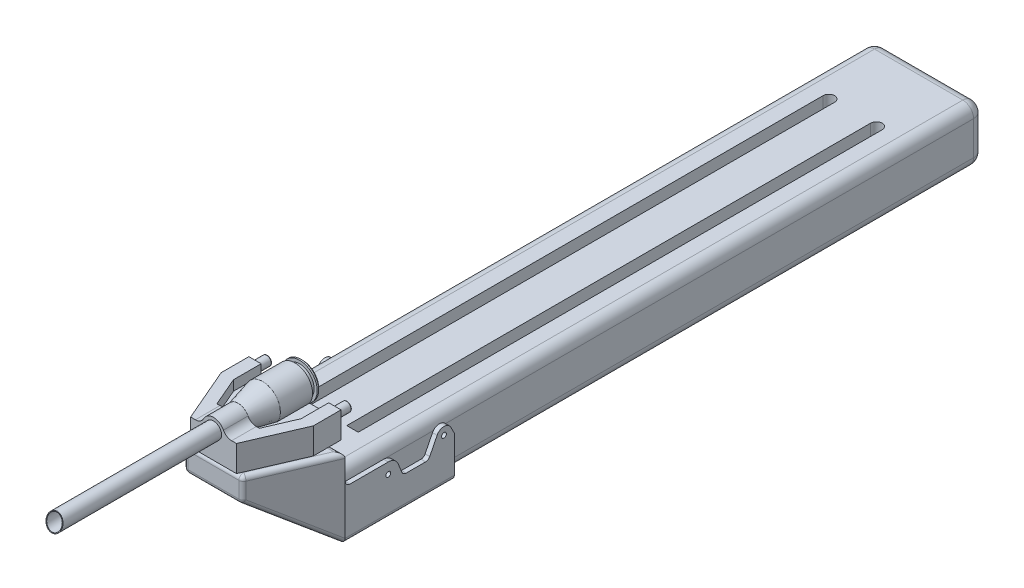
SolidWorks part; units mm, degrees
material "6061-T6 (SS)"
ref_plane "Front Plane" through (0, 0, 0) normal (0, 0, 1) x (1, 0, 0)
ref_plane "Top Plane" through (0, 0, 0) normal (0, 1, 0) x (1, 0, 0)
ref_plane "Right Plane" through (0, 0, 0) normal (1, 0, 0) x (0, 0, -1)
sketch "Sketch1" plane through (0, 0, 0) normal (0, 0, 1) x (1, 0, 0)
  line L1 (0, 0) -> (71.5, 0)
  line L2 (0, 0) -> (0, 36)
  line L3 (0, 36) -> (71.5, 36)
  line L4 (71.5, 0) -> (71.5, 36)
  dimension "D1" = 71.5
  dimension "D2" = 36
extrude "Boss-Extrude1" add sketch "Sketch1" along normal blind 419.1
sketch "Sketch2" plane through (0, 36, 0) normal (0, 1, 0) x (1, 0, 0)
  line L0 (71.5, -348.1) -> (74.5, -348.1)
  line L1 (74.5, -348.1) -> (74.5, -419.1)
  line L2 (74.5, -419.1) -> (54.25, -466.1)
  line L3 (54.25, -466.1) -> (17.25, -466.1)
  line L4 (71.5, 0) -> (0, 0)
  line L5 (0, 0) -> (0, -419.1)
  line L6 (0, -419.1) -> (71.5, -419.1)
  line L7 (71.5, -419.1) -> (71.5, 0)
  line L8 (71.5, 0) -> (0, 0)
  line L9 (0, 0) -> (0, -419.1)
  line L10 (0, -419.1) -> (71.5, -419.1)
  line L11 (71.5, -419.1) -> (71.5, 0)
  line L12 (17.25, -466.1) -> (-3, -419.1)
  line L13 (-3, -419.1) -> (-3, -348.1)
  line L14 (-3, -348.1) -> (0, -348.1)
  point P12 (35.75, -466.1)
  point P15 (35.75, -419.1)
  line M10 (0, -419.1) -> (71.5, -419.1)
  line M11 (71.5, -419.1) -> (71.5, 0)
  dimension "D2" = 47
  dimension "D3" = 3
  dimension "D4" = 3
  dimension "D5" = 37
  dimension "D6" = 71
  dimension "D1" = 0
extrude "Boss-Extrude2" add sketch "Sketch2" against normal blind 39 contours L14 L13 L12 L3 L2 L1 L0 L9 M11 M10 region at (35.75, 36, 432.1438)
sketch "Sketch3" plane through (0, -3, 0) normal (0, -1, 0) x (1, 0, 0)
  line L0 (71.5, 348.1) -> (0, 348.1)
  line L6 (0, 0) -> (71.5, 0)
  line L7 (71.5, 0) -> (71.5, 348.1)
  line L8 (71.5, 348.1) -> (71.5, 419.1)
  line L9 (71.5, 419.1) -> (0, 419.1)
  line L10 (0, 419.1) -> (0, 348.1)
  line L11 (0, 348.1) -> (0, 0)
  line L12 (0, 0) -> (71.5, 0)
  line L13 (71.5, 0) -> (71.5, 348.1)
  line L14 (71.5, 348.1) -> (71.5, 419.1)
  line L15 (71.5, 419.1) -> (0, 419.1)
  line L16 (0, 419.1) -> (0, 348.1)
  line L17 (0, 348.1) -> (0, 0)
  line M8 (0, 348.1) -> (0, 419.1)
  line M9 (0, 419.1) -> (71.5, 419.1)
  line M10 (71.5, 419.1) -> (71.5, 348.1)
  dimension "D1" = 0
extrude "Boss-Extrude3" add sketch "Sketch3" against normal up to surface (3 mm away) contours L0 M10 M9 M8 region at (35.75, -3, 383.6) up to face at (35.75, 0, 255.7333)
sketch "Sketch4" plane through (0, 36, 0) normal (0, 1, 0) x (1, 0, 0)
  line L0 (-3, -419.1) -> (74.5, -419.1)
  line L10 (0, 0) -> (0, -348.1)
  line L11 (0, -348.1) -> (-3, -348.1)
  line L12 (-3, -348.1) -> (-3, -419.1)
  line L13 (-3, -419.1) -> (17.25, -466.1)
  line L14 (17.25, -466.1) -> (54.25, -466.1)
  line L15 (54.25, -466.1) -> (74.5, -419.1)
  line L16 (74.5, -419.1) -> (74.5, -348.1)
  line L17 (74.5, -348.1) -> (71.5, -348.1)
  line L18 (71.5, -348.1) -> (71.5, 0)
  line L19 (71.5, 0) -> (0, 0)
  line L20 (0, 0) -> (0, -348.1)
  line L21 (0, -348.1) -> (-3, -348.1)
  line L22 (-3, -348.1) -> (-3, -419.1)
  line L23 (-3, -419.1) -> (17.25, -466.1)
  line L24 (17.25, -466.1) -> (54.25, -466.1)
  line L25 (54.25, -466.1) -> (74.5, -419.1)
  line L26 (74.5, -419.1) -> (74.5, -348.1)
  line L27 (74.5, -348.1) -> (71.5, -348.1)
  line L28 (71.5, -348.1) -> (71.5, 0)
  line L29 (71.5, 0) -> (0, 0)
  line M14 (-3, -419.1) -> (17.25, -466.1)
  line M15 (17.25, -466.1) -> (54.25, -466.1)
  line M16 (54.25, -466.1) -> (74.5, -419.1)
  dimension "D1" = 0
extrude "Boss-Extrude4" add sketch "Sketch4" along normal blind 12 contours L0 M14 M15 M16 region at (35.75, 36, 439.8293)
fillet "Fillet1" radius 7 8 edges at (0, 0, 174.05) (0, 36, 174.05) (71.5, 0, 174.05) (71.5, 36, 174.05) (0, 18, 0) (35.75, 0, 0) (71.5, 18, 0) (35.75, 36, 0)
sketch "Sketch10" plane through (0, 0, 0) normal (0, 0, -1) x (-1, 0, 0)
  line L4 (-62.5, 9) -> (-9, 9)
  line L5 (-62.5, 9) -> (-9, 9)
  line L6 (-9, 9) -> (-9, 27)
  line L7 (-9, 9) -> (-9, 27)
  line L8 (-9, 27) -> (-62.5, 27)
  line L9 (-9, 27) -> (-62.5, 27)
  line L10 (-62.5, 27) -> (-62.5, 9)
  line L11 (-62.5, 27) -> (-62.5, 9)
  dimension "D1" = 2
extrude "Cut-Extrude6" cut sketch "Sketch10" against normal up to surface (419.1 mm away) up to face at (35.75, 42, 419.1)
sketch "Sketch5" plane through (74.5, 0, 0) normal (1, 0, 0) x (0, 0, -1)
  line L0 (-419.1, -3) -> (-466.1, 33)
  line L1 (-466.1, -3) -> (-466.1, 48) construction
  line L2 (-466.1, -3) -> (-466.1, 48)
  line L3 (-419.1, -3) -> (-466.1, -3)
  dimension "D1" = 15
extrude "Cut-Extrude1" cut sketch "Sketch5" against normal up to surface (77.5 mm away) contours L3 L0 L2 region at (74.5, 9, 450.4333) up to face at (-3, 16.5, 383.6)
sketch "Sketch6" plane through (74.5, 0, 0) normal (1, 0, 0) x (0, 0, -1)
  line L0 (-419.1, 48) -> (-419.1, 36) construction
  line L1 (-391.1, 29) -> (-419.1, 29)
  line L2 (-366.7644, 16.88) -> (-379.4356, 16.88)
  line L3 (-382.2134, 18.747) -> (-384.6184, 24.6436)
  line L4 (-348.1, 36) -> (-419.1, 36)
  line L5 (-419.1, 36) -> (-419.1, -3)
  line L6 (-419.1, -3) -> (-348.1, -3)
  line L7 (-348.1, -3) -> (-348.1, 36)
  line L8 (-348.1, 36) -> (-419.1, 36)
  line L9 (-419.1, 36) -> (-419.1, -3)
  line L10 (-419.1, -3) -> (-348.1, -3)
  line L11 (-348.1, -3) -> (-348.1, 36)
  line L12 (-364.0826, 18.5354) -> (-359.2765, 28.121)
  line L13 (-348.1, 23.8363) -> (-350.3743, 28.1936)
  circle A0 centre (-354.8068, 25.88) radius 1.5875
  circle A1 centre (-391.1, 22) radius 1.59
  arc A2 (-384.6184, 24.6436) -> (-391.1, 29) centre (-391.1, 22) ccw
  arc A4 (-364.0826, 18.5354) -> (-366.7644, 16.88) centre (-366.7644, 19.88) cw
  arc A5 (-379.4356, 16.88) -> (-382.2134, 18.747) centre (-379.4356, 19.88) cw
  circle A6 centre (-354.8068, 25.88) radius 5
  point P16 (-373.1, 16.88)
  point P20 (-364.9126, 16.88)
  point P23 (-381.452, 16.88)
  line M6 (-348.1, 36) -> (-419.1, 36)
  line M7 (-419.1, 36) -> (-419.1, -3)
  dimension "D2" = 3.18
  dimension "D6" = 14
  dimension "D10" = 3
  dimension "D8" = 3.175
  dimension "D12" = 10
  dimension "D3" = 36.5
  dimension "D4" = 28
  dimension "D5" = 14
  dimension "D7" = 9
  dimension "D9" = 18
  dimension "D11" = 3.88
  dimension "D1" = 0
extrude "Cut-Extrude2" cut sketch "Sketch6" against normal blind 3 contours A6 L13 L11 L1 A2 L3 A5 L2 A4 L12 M6 M7 region at (74.5, 29.3231, 379.9491)
sketch "Sketch7" plane through (0, 0, 348.1) normal (0, 0, -1) x (-1, 0, 0)
  line L2 (-64.5, 36) -> (-71.5, 36)
  line L3 (-71.5, 36) -> (-71.5, 29)
  line L4 (-64.5, 36) -> (-71.5, 36)
  line L5 (-71.5, 36) -> (-71.5, 29)
  arc A1 (-64.5, 36) -> (-71.5, 29) centre (-64.5, 29) ccw
  arc A2 (-64.5, 36) -> (-71.5, 29) centre (-64.5, 29) ccw
  dimension "D1" = 0
extrude "Cut-Extrude3" cut sketch "Sketch7" against normal up to surface (71 mm away) up to face at (47.6667, 37.6667, 419.1)
ref_plane "Plane1" through (35.75, 0, 0) normal (1, 0, 0) x (0, 0, -1)
mirror "Mirror2" about plane through (35.75, 0, 0) normal (1, 0, 0) of "Cut-Extrude2", "Cut-Extrude3"
fillet "Fillet2" radius 3 13 edges at (-3, -3, 383.6) (74.5, -3, 383.6) (64.375, 15, 442.6) (17.25, 40.5, 466.1) (35.75, 33, 466.1) (7.125, 15, 442.6) (7.125, 48, 442.6) (35.75, 48, 466.1) (54.25, 40.5, 466.1) (35.75, 48, 419.1) (64.375, 48, 442.6) (-1.5, 29, 419.1) (73, 29, 419.1)
sketch "Sketch9" plane through (0, 36, 0) normal (0, 1, 0) x (1, 0, 0)
  line L0 (7, -419.1) -> (64.5, -419.1) construction
  line L2 (16.5, -50) -> (16.5, -391.1)
  line L3 (16.5, -391.1) -> (24, -391.1)
  line L4 (24, -50) -> (24, -391.1)
  line L5 (47.5, -391.1) -> (55, -391.1)
  line L6 (47.5, -391.1) -> (47.5, -50)
  line L8 (55, -391.1) -> (55, -50)
  line L9 (64.5, 0) -> (7, 0) construction
  line L10 (24, -50) -> (47.5, -50) construction
  arc A0 (55, -50) -> (47.5, -50) centre (51.25, -50) ccw
  arc A1 (24, -50) -> (16.5, -50) centre (20.25, -50) ccw
  point P8 (35.75, -50)
  point P9 (35.75, 0)
  dimension "D1" = 28
  dimension "D2" = 23.5
  dimension "D3" = 7.5
  dimension "D4" = 50
extrude "Cut-Extrude5" cut sketch "Sketch9" against normal blind 12 contours L8 A0 L6 L5 | L2 L3 L4 A1 region at (51.25, 36, 219.0764)
extrude "Cut-Extrude4" cut sketch "Sketch6<3>" against normal up to surface (77.5 mm away) contours A1 | A0 region at (74.5, 22, 391.1) up to face at (-3, 20.6248, 379.1073)
sketch "Sketch6<3>" plane through (74.5, 0, 0) normal (1, 0, 0) x (0, 0, -1) same geometry as "Sketch6"
sketch "Sketch11" plane through (0, 0, 0) normal (0, 0, -1) x (-1, 0, 0)
  line L4 (-64.5, 7) -> (-7, 7)
  line L5 (-64.5, 7) -> (-7, 7)
  line L6 (-7, 7) -> (-7, 29)
  line L7 (-7, 7) -> (-7, 29)
  line L12 (-7, 29) -> (-64.5, 29)
  line L13 (-7, 29) -> (-64.5, 29)
  line L14 (-64.5, 29) -> (-64.5, 7)
  line L15 (-64.5, 29) -> (-64.5, 7)
  dimension "D1" = 0
extrude "Boss-Extrude5" add sketch "Sketch11" against normal blind 2
sketch "Sketch12" plane through (35.75, 0, 0) normal (1, 0, 0) x (0, 0, -1)
  line L0 (0, 18) -> (7.2687, 18)
  line L1 (0, 7) -> (0, 29) construction
  line L2 (0, 7) -> (0, 29)
  line L3 (2, 12.6087) -> (2, 14)
  line L4 (3.8559, 18) -> (3.8559, 20.5172) construction
  line L5 (2.9217, 20.9859) -> (0, 17.7695)
  arc A0 (0, 12) -> (2, 12.6087) centre (-1.1532, 19.3794) ccw
  arc A1 (2, 14) -> (3.8559, 18) centre (-1.3825, 18) ccw
  dimension "D1" = 2
  dimension "D2" = 6
  dimension "D3" = 4
revolve "Revolve1" add sketch "Sketch12" angle 360 about L0 region at (35.75, 15.5332, -1.5335)
sketch "Sketch13" plane through (0, 48, 0) normal (0, 1, 0) x (1, 0, 0)
  line L0 (5.75, -413.1) -> (5.75, -431.1)
  line L2 (5.75, -431.1) -> (20.8298, -466.1)
  line L3 (52.276, -466.1) -> (19.224, -466.1) construction
  line L4 (52.276, -466.1) -> (19.224, -466.1)
  line L5 (50.6702, -466.1) -> (65.75, -431.1)
  line L6 (65.75, -431.1) -> (65.75, -413.1)
  line L7 (65.75, -413.1) -> (5.75, -413.1)
  line L12 (1.5592, -422.1) -> (19.224, -463.1) construction
  line L13 (52.276, -463.1) -> (69.9408, -422.1) construction
  line L14 (-3, -419.1) -> (74.5, -419.1) construction
  point P12 (35.75, -466.1)
  point P14 (35.75, -413.1)
  line M9 (69.9408, -422.1) -> (1.5592, -422.1)
  line M11 (19.224, -463.1) -> (52.276, -463.1)
  dimension "D1" = 60
  dimension "D2" = 18
  dimension "D3" = 6
extrude "Boss-Extrude6" add sketch "Sketch13" along normal blind 10.5 contours L5 L6 L0 L2 M9 M11 | L6 L7 L0 M9 | L4 L5 L2 M11 region at (35.75, 48, 417.6) region at (35.75, 48, 440.451) region at (35.75, 48, 464.5792)
sketch "Sketch14" plane through (0, 58.5, 0) normal (0, 1, 0) x (1, 0, 0)
  line L0 (13.75, -413.1) -> (13.75, -431.1)
  line L1 (13.75, -431.1) -> (21.9362, -450.1)
  line L2 (21.9362, -450.1) -> (49.5638, -450.1)
  line L3 (49.5638, -450.1) -> (57.75, -431.1)
  line L4 (57.75, -431.1) -> (57.75, -413.1)
  line L6 (50.6702, -466.1) -> (65.75, -431.1)
  line L7 (65.75, -431.1) -> (65.75, -413.1)
  line L8 (65.75, -413.1) -> (5.75, -413.1)
  line L9 (5.75, -413.1) -> (5.75, -431.1)
  line L10 (5.75, -431.1) -> (20.8298, -466.1)
  line L11 (20.8298, -466.1) -> (50.6702, -466.1)
  line L12 (50.6702, -466.1) -> (65.75, -431.1)
  line L13 (65.75, -431.1) -> (65.75, -413.1)
  line L14 (65.75, -413.1) -> (5.75, -413.1)
  line L15 (5.75, -413.1) -> (5.75, -431.1)
  line L16 (5.75, -431.1) -> (20.8298, -466.1)
  line L17 (20.8298, -466.1) -> (50.6702, -466.1)
  line M12 (50.6702, -466.1) -> (65.75, -431.1)
  line M13 (65.75, -431.1) -> (65.75, -413.1)
  line M14 (65.75, -413.1) -> (5.75, -413.1)
  line M15 (5.75, -413.1) -> (5.75, -431.1)
  line M16 (5.75, -431.1) -> (20.8298, -466.1)
  line M17 (20.8298, -466.1) -> (50.6702, -466.1)
  dimension "D2" = 8
  dimension "D3" = 8
  dimension "D4" = 16
  dimension "D1" = 0
extrude "Boss-Extrude7" add sketch "Sketch14" along normal blind 6.5 contours L4 L3 L2 L1 L0 M14 M15 M16 M17 M12 M13 region at (12.9494, 58.5, 422.1)
sketch "Sketch15" plane through (0, 0, 413.1) normal (0, 0, -1) x (-1, 0, 0)
  line L0 (-65.75, 65) -> (-57.75, 65) construction
  line L1 (-13.75, 65) -> (-5.75, 65) construction
  circle A0 centre (-9.75, 61) radius 3
  circle A1 centre (-61.75, 61.0466) radius 3
  point P4 (-9.75, 65)
  point P5 (-61.75, 65)
  dimension "D1" = 6
  dimension "D2" = 4
extrude "Boss-Extrude8" add sketch "Sketch15" along normal blind 8
sketch "Sketch16" plane through (35.75, 0, 0) normal (1, 0, 0) x (0, 0, -1)
  line L0 (104.5951, 65) -> (-584.1857, 65) construction
  line L2 (-450.1, 65) -> (-450.1, 58.5) construction
  line L3 (-450.1, 65) -> (-450.1, 58.5)
  line L4 (-466.1, 65) -> (-466.1, 48) construction
  line L5 (-466.1, 65) -> (-466.1, 48)
  line L6 (-408.1, 73.5) -> (-408.1, 65)
  line L7 (-450.1, 72.25) -> (-466.1, 72.25)
  line L8 (-466.1, 72.25) -> (-466.1, 70.25)
  line L9 (-466.1, 70.25) -> (-571.4, 70.25)
  line L10 (-450.1, 72.25) -> (-434.1, 76.5)
  line L11 (-434.1, 76.5) -> (-413.1, 76.5)
  line L12 (-571.4, 70.25) -> (-571.4, 69.8)
  line L13 (-571.4, 69.8) -> (-457.5707, 69.8)
  line L14 (-443.6413, 73.5) -> (-457.5707, 69.8)
  line L15 (-443.6413, 73.5) -> (-408.1, 73.5)
  line L16 (-408.1, 73.5) -> (-408.1, 75.5)
  line L17 (-408.1, 65) -> (-571.4, 65)
  line L18 (-571.4, 65) -> (-571.4, 69.8)
  line L19 (-410.1, 76.5) -> (-410.1, 74.5)
  line L20 (-410.1, 74.5) -> (-413.1, 74.5)
  line L21 (-413.1, 74.5) -> (-413.1, 76.5)
  line L22 (-409.1, 76.5) -> (-408.1, 75.5)
  line L23 (-410.1, 76.5) -> (-409.1, 76.5)
  circle A0 centre (-534.81, 65) radius 11.7519 construction
  circle A1 centre (-391.1, 22) radius 1.59 construction
  circle A2 centre (-391.1, 22) radius 1.59
  point P15 (-408.1, 76.5)
  dimension "D2" = 2
  dimension "D3" = 10.5
  dimension "D4" = 26
  dimension "D5" = 16
  dimension "D6" = 11.5
  dimension "D7" = 0.45
  dimension "D8" = 3
  dimension "D9" = 0.45
  dimension "D10" = 105.3
  dimension "D11" = 3
  dimension "D12" = 2
  dimension "D13" = 2
  dimension "D14" = 143.71
  dimension "D15" = 43
revolve "Cut-Revolve1" cut sketch "Sketch16" angle 360 about L0 region at (35.75, 68.0933, 479.6887)
revolve "Revolve3" add sketch "Sketch16<4>" angle 360 about L0 region at (35.75, 75.1344, 425.8706)
sketch "Sketch16<4>" plane through (35.75, 0, 0) normal (1, 0, 0) x (0, 0, -1) same geometry as "Sketch16"
fillet "Fillet3" radius 6 2 edges at (28.5, 65, 458.1) (43, 65, 458.1)
fillet "Fillet4" radius 0.5 2 edges at (6.75, 61, 405.1) (58.75, 61.0466, 405.1)
sketch "Sketch17" plane through (35.75, 0, 0) normal (1, 0, 0) x (0, 0, -1)
  line L0 (-571.4, 70.25) -> (-571.4, 59.75) construction
  line L1 (-571.4, 70.25) -> (-571.4, 59.75)
  line L2 (-571.4, 59.75) -> (-567.9, 70.25)
  line L3 (-466.1, 70.25) -> (-571.4, 70.25) construction
  line L4 (-567.9, 70.25) -> (-571.4, 70.25)
  dimension "D1" = 3.5
extrude "Cut-Extrude7" cut sketch "Sketch17" along normal through all both and the other way through all
ref_plane "Plane2" through (0, 61.5352, 6.5828) normal (0, 0.9943, 0.1064) x (1, 0, 0)
equation "\"`60\"=57.8211"
equation "\"`8\"=5.50577"
